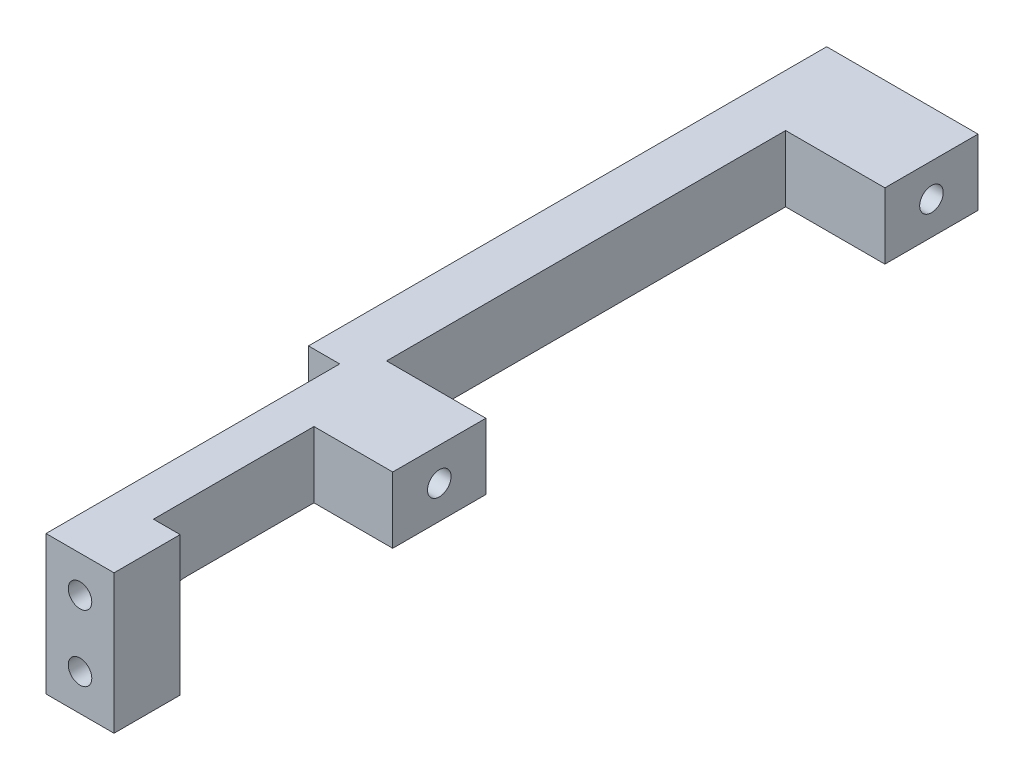
SolidWorks part; units mm, degrees
ref_plane "Front" through (0, 0, 0) normal (0, 0, 1) x (1, 0, 0)
ref_plane "Top" through (0, 0, 0) normal (0, 1, 0) x (1, 0, 0)
ref_plane "Right" through (0, 0, 0) normal (1, 0, 0) x (0, 0, -1)
sketch "Sketch1" plane through (0, 0, 0) normal (0, 1, 0) x (1, 0, 0)
  line L1 (-5.7672, 38.989) -> (5.7672, 38.989)
  line L2 (-5.7672, 38.989) -> (-5.7672, -38.989)
  line L3 (-5.7672, -38.989) -> (5.7672, -38.989)
  line L4 (5.7672, 38.989) -> (5.7672, -38.989)
  line L5 (-5.7672, 38.989) -> (5.7672, -38.989) construction
  line L6 (-5.7672, -38.989) -> (5.7672, 38.989) construction
  point P0 (0, 0)
  dimension "D1" = 77.978
  dimension "D2" = 11.5344
extrude "Boss-Extrude1" add sketch "Sketch1" along normal blind 6.35
hole_wizard "#4-40 Tapped Hole1" positions "Sketch3" profile "Sketch4" tap size "#4-40" standard "ANSI Inch"
sketch "Sketch3" plane through (5.7672, 0, 0) normal (1, 0, 0) x (0, 0, -1)
  line L0 (34.5186, 3.175) -> (-12.7508, 3.175)
  line L2 (38.989, 6.35) -> (38.989, 0) construction
  line L3 (38.989, 6.35) -> (34.5186, 3.175)
  line L6 (34.5186, 3.175) -> (38.989, 0)
  point P0 (34.5186, 3.175)
  point P2 (-12.7508, 3.175)
  dimension "D1" = 47.2694
  dimension "D2" = 4.4704
cosmetic thread "Hole Thread1" parameters "D1"=6.096, "D2"=2.8448
cosmetic thread "Hole Thread2" parameters "D1"=6.096, "D2"=2.8448
sketch "Sketch4" plane through (5.7672, 3.175, -34.5186) normal (0, 1, 0) x (0, 0, -1)
  line L0 (0, 0) -> (0, 7.0292)
  line L1 (0, 7.0292) -> (1.1303, 6.35)
  line L2 (1.1303, 6.35) -> (1.1303, 0)
  line L5 (1.1303, 0) -> (0, 0)
  line L10 (0, 7.0292) -> (-1.1303, 6.35) construction
  line L11 (0, -6.35) -> (0, 107.95) construction
  dimension "Tap Drill Dia." = 2.2606
  dimension "Tap Drill Depth" = 6.35
  dimension "Drill Angle" = 118
sketch "Sketch2" plane through (0, 6.35, 0) normal (0, 1, 0) x (1, 0, 0)
  line L0 (5.7672, -38.989) -> (5.7672, 38.989) construction
  line L1 (-3.7672, 30.0482) -> (5.7672, 30.0482)
  line L2 (-3.7672, 30.0482) -> (-3.7672, -8.2804)
  line L3 (-3.7672, -8.2804) -> (5.7672, -8.2804)
  line L4 (5.7672, 30.0482) -> (5.7672, -8.2804)
  line L5 (-3.7672, 30.0482) -> (5.7672, -8.2804) construction
  line L6 (-3.7672, -8.2804) -> (5.7672, 30.0482) construction
  line L7 (5.7672, 33.3883) -> (5.7672, 35.6489) construction
  line L8 (-1.7985, -32.639) -> (5.7672, -32.639)
  line L9 (-1.7985, -32.639) -> (-1.7985, -17.2212)
  line L10 (-1.7985, -17.2212) -> (5.7672, -17.2212)
  line L11 (5.7672, -32.639) -> (5.7672, -17.2212)
  line L12 (-1.7985, -32.639) -> (5.7672, -17.2212) construction
  line L13 (-1.7985, -17.2212) -> (5.7672, -32.639) construction
  line L14 (5.7672, 33.3883) -> (5.7672, 35.6489) construction
  line L15 (5.7672, 35.6489) -> (5.7672, 38.989) construction
  line L16 (5.7672, 33.3883) -> (5.7672, 30.0482) construction
  line L17 (5.7672, 33.3883) -> (5.7672, 35.6489) construction
  line L19 (5.7672, -13.8811) -> (5.7672, -11.6205) construction
  line L20 (5.7672, -13.8811) -> (5.7672, -11.6205) construction
  line L21 (5.7672, -11.6205) -> (5.7672, -8.2804) construction
  line L22 (5.7672, -13.8811) -> (5.7672, -17.2212) construction
  line L23 (-5.7672, 38.989) -> (-5.7672, -38.989) construction
  line L24 (-5.7672, -38.989) -> (5.7672, -38.989) construction
  point P0 (1, 10.8839)
  point P8 (1.9844, -24.9301)
  dimension "D1" = 2
  dimension "D2" = 3.9688
  dimension "D3" = 6.35
extrude "Cut-Extrude1" cut sketch "Sketch2" against normal through all
sketch "Sketch8" plane through (0, 6.35, 0) normal (0, 1, 0) x (1, 0, 0)
  line L1 (0.7672, -38.989) -> (5.7672, -38.989)
  line L2 (0.7672, -38.989) -> (0.7672, -32.639)
  line L3 (0.7672, -32.639) -> (5.7672, -32.639)
  line L4 (5.7672, -38.989) -> (5.7672, -32.639)
  line L5 (0.7672, -38.989) -> (5.7672, -32.639) construction
  line L6 (0.7672, -32.639) -> (5.7672, -38.989) construction
  point P0 (3.2672, -35.814)
  point P6 (0, 0)
  dimension "D1" = 5
extrude "Cut-Extrude2" cut sketch "Sketch8" against normal through all
sketch "Sketch9" plane through (0, 0, 38.989) normal (0, 0, 1) x (1, 0, 0)
  line L1 (-5.7672, -7) -> (0.7672, -7)
  line L2 (-5.7672, -7) -> (-5.7672, 0)
  line L3 (-5.7672, 0) -> (0.7672, 0)
  line L4 (0.7672, -7) -> (0.7672, 0)
  line L5 (-5.7672, -7) -> (0.7672, 0) construction
  line L6 (-5.7672, 0) -> (0.7672, -7) construction
  point P0 (-2.5, -3.5)
  point P5 (0, 0)
  point P6 (0, 0)
  dimension "D1" = 7
extrude "Boss-Extrude2" add sketch "Sketch9" against normal up to surface (6.35 mm away) up to face at (-0.5156, 3.175, 32.639)
hole_wizard "#4-40 Tapped Hole2" positions "Sketch5" profile "Sketch7" tap size "#4-40" standard "ANSI Inch"
sketch "Sketch5" plane through (0, 0, 38.989) normal (0, 0, 1) x (1, 0, 0)
  line L0 (-5.7672, 6.35) -> (-2.5, 2.85) construction
  line L1 (-2.5, 2.85) -> (-2.5, -3.5) construction
  line L2 (-2.5, -3.5) -> (0.7672, -7) construction
  line L4 (-2.5, -3.5) -> (-5.7672, -7) construction
  line L5 (-2.5, 2.85) -> (0.7672, 6.35) construction
  line L6 (-5.7672, 6.35) -> (0.7672, 6.35) construction
  point P0 (-2.5, 2.85)
  point P2 (-2.5, -3.5)
  point P28 (0, 0)
  point P29 (0, 0)
  point P30 (0, 0)
  point P31 (5.1541, 0.4017)
  point P32 (0, 0)
  point P33 (0, 0)
  point P35 (0, 0)
  point P37 (-3.7828, 1.6412)
  point P38 (0, 0)
  point P39 (1.7067, 5.0629)
  dimension "D1" = 3.5
sketch "Sketch7" plane through (-2.5, 2.85, 38.989) normal (1, 0, 0) x (0, -1, 0)
  line L0 (0, 0) -> (0, 5.6792)
  line L1 (0, 5.6792) -> (1.1303, 5)
  line L2 (1.1303, 5) -> (1.1303, 0)
  line L5 (1.1303, 0) -> (0, 0)
  line L10 (0, 5.6792) -> (-1.1303, 5) construction
  line L11 (0, -6.35) -> (0, 107.95) construction
  dimension "Tap Drill Dia." = 2.2606
  dimension "Tap Drill Depth" = 5
  dimension "Drill Angle" = 118
cosmetic thread "Hole Thread4" parameters "D1"=5, "D2"=2.8448
cosmetic thread "Hole Thread5" parameters "D1"=5, "D2"=2.8448
sketch "Sketch10" plane through (0, 0, 0) normal (0, -1, 0) x (1, 0, 0)
  line L0 (-5.7672, -38.989) -> (-5.7672, 32.639) construction
  line L1 (-8.7672, 10.7804) -> (-5.7672, 10.7804)
  line L2 (-8.7672, 10.7804) -> (-8.7672, -38.989)
  line L3 (-8.7672, -38.989) -> (-5.7672, -38.989)
  line L4 (-5.7672, 10.7804) -> (-5.7672, -38.989)
  line L5 (-8.7672, 10.7804) -> (-5.7672, -38.989) construction
  line L6 (-8.7672, -38.989) -> (-5.7672, 10.7804) construction
  line L8 (-3.7672, 8.2804) -> (5.7672, 8.2804) construction
  point P0 (-7.2672, -14.1043)
  point P6 (-5.7672, 18.1792)
  point P9 (-5.7672, 12.0121)
  point P11 (0, 0)
  point P12 (0, 0)
  point P13 (0, 0)
  point P14 (0, 0)
  point P15 (0, 0)
  dimension "D1" = 3
  dimension "D2" = 2.5
extrude "Boss-Extrude3" add sketch "Sketch10" against normal up to surface (6.35 mm away) up to face at (0.1615, 6.35, 4.6821)
fillet "Fillet1" radius 3.175 1 edges at (-3.7828, 0, 32.639)
